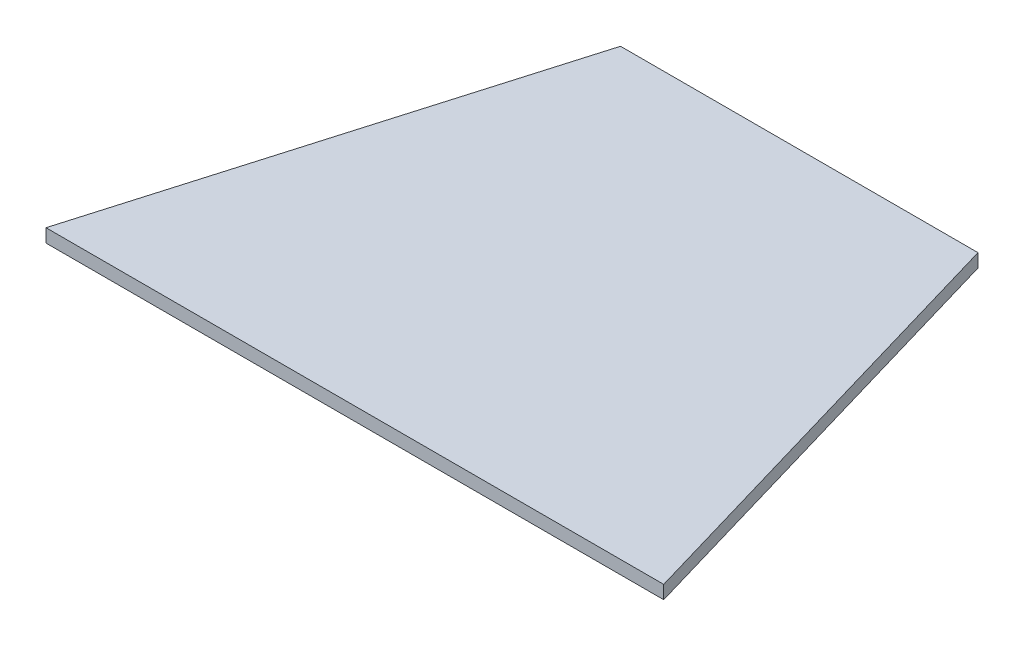
SolidWorks part; units mm, degrees
ref_plane "Front Plane" through (0, 0, 0) normal (0, 0, 1) x (1, 0, 0)
ref_plane "Top Plane" through (0, 0, 0) normal (0, 1, 0) x (1, 0, 0)
ref_plane "Right Plane" through (0, 0, 0) normal (1, 0, 0) x (0, 0, -1)
sketch "Sketch1" plane through (0, 0, 0) normal (0, 1, 0) x (1, 0, 0)
  line L0 (0, 0) -> (139, 0)
  line L1 (0, 0) -> (29.2799, 100)
  line L2 (139, 0) -> (109.7201, 100)
  line L3 (66.5, 0) -> (66.5, 100) construction
  line L4 (29.2799, 100) -> (109.7201, 100)
extrude "Boss-Extrude1" add sketch "Sketch1" along normal blind 3
